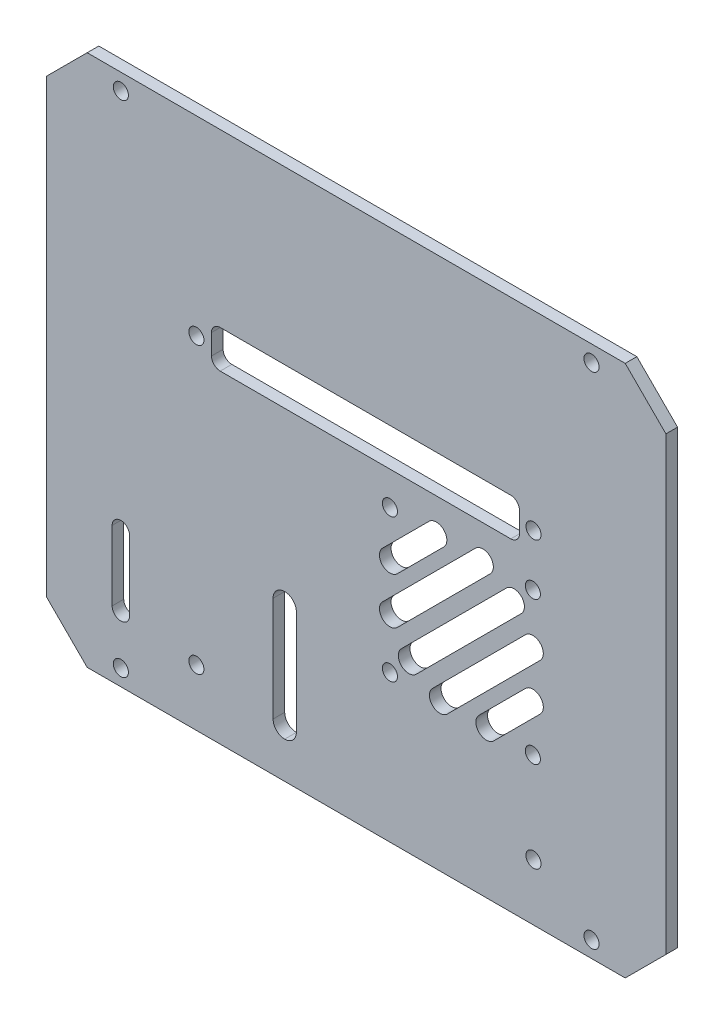
SolidWorks part; units mm, degrees
ref_plane "前视基准面" through (0, 0, 0) normal (0, 0, 1) x (1, 0, 0)
ref_plane "上视基准面" through (0, 0, 0) normal (0, 1, 0) x (1, 0, 0)
ref_plane "右视基准面" through (0, 0, 0) normal (1, 0, 0) x (0, 0, -1)
sketch "草图2" plane through (0, 0, -42.2) normal (0, 0, -1) x (-1, 0, 0)
  line L32 (-57.3467, -34.0538) -> (-50.3426, -41.058)
  line L33 (-50.3426, -41.058) -> (42.2491, -41.058)
  line L34 (42.2491, -41.058) -> (49.2533, -34.0538)
  line L35 (49.2533, -34.0538) -> (49.2533, 43.5378)
  line L36 (49.2533, 43.5378) -> (42.2491, 50.542)
  line L37 (-57.3467, 43.5378) -> (-57.3467, -34.0538)
  line L38 (-50.3426, 50.542) -> (-57.3467, 43.5378)
  line L39 (42.2491, 50.542) -> (-50.3426, 50.542)
  line L40 (-57.3467, -34.0538) -> (-50.3426, -41.058)
  line L41 (-50.3426, -41.058) -> (42.2491, -41.058)
  line L42 (42.2491, -41.058) -> (49.2533, -34.0538)
  line L43 (49.2533, -34.0538) -> (49.2533, 43.5378)
  line L44 (49.2533, 43.5378) -> (42.2491, 50.542)
  line L45 (-57.3467, 43.5378) -> (-57.3467, -34.0538)
  line L46 (-50.3426, 50.542) -> (-57.3467, 43.5378)
  line L47 (42.2491, 50.542) -> (-50.3426, 50.542)
  dimension "D1" = 0.2
extrude "凸台-拉伸1" add sketch "草图2" along normal blind 2
sketch "草图3" plane through (0, 0, -44.2) normal (0, 0, -1) x (-1, 0, 0)
  circle A0 centre (-44.5467, -38.258) radius 1.3
  circle A1 centre (36.4533, -38.258) radius 1.3
  circle A2 centre (-44.5467, 47.742) radius 1.3
  circle A3 centre (36.4533, 47.742) radius 1.3
  dimension "D1" = 2.6
extrude "切除-拉伸1" cut sketch "草图3" against normal through all
sketch "草图4" plane through (0, 0, -44.2) normal (0, 0, -1) x (-1, 0, 0)
  circle A1 centre (23.4533, -31.2932) radius 1.3
  circle A2 centre (23.4533, -31.2932) radius 1.3
  circle A3 centre (-34.5583, -31.2932) radius 1.3
  circle A4 centre (-34.5583, -31.2932) radius 1.3
  circle A5 centre (23.4533, 17.742) radius 1.3
  circle A6 centre (23.4533, 17.742) radius 1.3
  circle A7 centre (-34.5583, 17.742) radius 1.3
  circle A8 centre (-34.5583, 17.742) radius 1.3
  dimension "D1" = 0
  dimension "D2" = 0
  dimension "D3" = 0
  dimension "D4" = 0
extrude "切除-拉伸2" cut sketch "草图4" against normal up to next
sketch "草图5" plane through (0, 0, -44.2) normal (0, 0, -1) x (-1, 0, 0)
  line L0 (-50.4254, -41.258) -> (42.3319, -41.258) construction
  line L1 (-32.1467, 14.542) -> (20.8533, 14.542)
  line L2 (-32.1467, 14.542) -> (-32.1467, 21.042)
  line L3 (-32.1467, 21.042) -> (20.8533, 21.042)
  line L4 (20.8533, 14.542) -> (20.8533, 21.042)
  line L7 (-57.3467, 43.5378) -> (-57.3467, -34.0538) construction
  dimension "D1" = 53
  dimension "D2" = 6.5
  dimension "D3" = 25.2
  dimension "D4" = 55.8
extrude "切除-拉伸3" cut sketch "草图5" against normal up to next
fillet "圆角1" radius 1.5 4 edges at (32.1467, 21.042, -43.2) (32.1467, 14.542, -43.2) (-20.8533, 14.542, -43.2) (-20.8533, 21.042, -43.2)
sketch "草图7" plane through (0, 0, -44.2) normal (0, 0, -1) x (-1, 0, 0)
  line L0 (-59.0467, 44.242) -> (-59.0467, -34.758) construction
  line L1 (42.9533, 52.242) -> (-51.0467, 52.242) construction
  circle A0 centre (-34.4467, 8.842) radius 1.3
  circle A1 centre (-34.4467, -15.758) radius 1.3
  circle A2 centre (-9.8467, 8.842) radius 1.3
  circle A3 centre (-9.8467, -15.758) radius 1.3
  dimension "D1" = 24.6
  dimension "D2" = 24.6
  dimension "D3" = 24.6
  dimension "D4" = 43.4
extrude "切除-拉伸4" cut sketch "草图7" against normal up to next
sketch "草图8" plane through (0, 0, -44.2) normal (0, 0, -1) x (-1, 0, 0)
  line L0 (-34.4467, 8.842) -> (-9.8467, -15.758) construction
  line L1 (-34.4467, 8.842) -> (-9.8467, 8.842) construction
  line L2 (-34.4467, 8.842) -> (-34.4467, -15.758) construction
  line L3 (-34.4467, -15.758) -> (-9.8467, -15.758) construction
  line L4 (-9.8467, 8.842) -> (-9.8467, -15.758) construction
  line L5 (-31.194, 5.5893) -> (-13.0994, -12.5053) construction
  line L6 (-29.9212, 6.8621) -> (-11.8266, -11.2325)
  line L7 (-32.4668, 4.3165) -> (-14.3722, -13.7781)
  line L8 (-34.4467, 0.242) -> (-18.4467, -15.758) construction
  line L9 (-33.1739, 1.5148) -> (-17.1739, -14.4852)
  line L10 (-35.7195, -1.0308) -> (-19.7195, -17.0308)
  line L11 (-25.8467, 8.842) -> (-9.8467, -7.158) construction
  line L12 (-24.5739, 10.1148) -> (-8.5739, -5.8852)
  line L13 (-27.1195, 7.5692) -> (-11.1195, -8.4308)
  line L14 (-17.8467, 8.842) -> (-9.8467, 0.842) construction
  line L15 (-16.5739, 10.1148) -> (-8.5739, 2.1148)
  line L16 (-19.1195, 7.5692) -> (-11.1195, -0.4308)
  line L17 (-34.4467, -7.758) -> (-26.4467, -15.758) construction
  line L18 (-33.1739, -6.4852) -> (-25.1739, -14.4852)
  line L19 (-35.7195, -9.0308) -> (-27.7195, -17.0308)
  line L20 (42.9533, 52.242) -> (-51.0467, 52.242) construction
  line L22 (-59.0467, 44.242) -> (-59.0467, -34.758) construction
  arc A1 (-29.9212, 6.8621) -> (-32.4668, 4.3165) centre (-31.194, 5.5893) ccw
  arc A2 (-14.3722, -13.7781) -> (-11.8266, -11.2325) centre (-13.0994, -12.5053) ccw
  arc A3 (-33.1739, 1.5148) -> (-35.7195, -1.0308) centre (-34.4467, 0.242) ccw
  arc A4 (-19.7195, -17.0308) -> (-17.1739, -14.4852) centre (-18.4467, -15.758) ccw
  arc A5 (-24.5739, 10.1148) -> (-27.1195, 7.5692) centre (-25.8467, 8.842) ccw
  arc A6 (-11.1195, -8.4308) -> (-8.5739, -5.8852) centre (-9.8467, -7.158) ccw
  arc A7 (-16.5739, 10.1148) -> (-19.1195, 7.5692) centre (-17.8467, 8.842) ccw
  arc A8 (-11.1195, -0.4308) -> (-8.5739, 2.1148) centre (-9.8467, 0.842) ccw
  arc A9 (-33.1739, -6.4852) -> (-35.7195, -9.0308) centre (-34.4467, -7.758) ccw
  arc A10 (-27.7195, -17.0308) -> (-25.1739, -14.4852) centre (-26.4467, -15.758) ccw
  point P10 (-22.1467, -3.458)
  point P15 (-26.4467, -7.758)
  point P22 (-17.8467, 0.842)
  point P29 (-13.8467, 4.842)
  point P36 (-30.4467, -11.758)
  dimension "D1" = 1.8
  dimension "D2" = 1.8
  dimension "D3" = 1.8
  dimension "D4" = 1.8
  dimension "D5" = 1.8
  dimension "D6" = 8
  dimension "D7" = 8
  dimension "D8" = 8
  dimension "D9" = 8
  dimension "D10" = 4.6
  dimension "D11" = 4.6
  dimension "D12" = 43.4
  dimension "D13" = 68
  dimension "D14" = 24.6
extrude "切除-拉伸5" cut sketch "草图8" against normal up to next
sketch "草图9" plane through (0, 0, -44.2) normal (0, 0, -1) x (-1, 0, 0)
  line L0 (49.2533, -34.0538) -> (49.2533, 43.5378) construction
  line L1 (6.2533, -12.758) -> (10.2533, -12.758)
  line L2 (6.2533, -12.758) -> (6.2533, -34.758)
  line L3 (6.2533, -34.758) -> (10.2533, -34.758)
  line L4 (10.2533, -12.758) -> (10.2533, -34.758)
  line L6 (-51.0467, -42.758) -> (42.9533, -42.758) construction
  dimension "D1" = 39
  dimension "D2" = 4
  dimension "D3" = 22
  dimension "D4" = 8
extrude "切除-拉伸6" cut sketch "草图9" against normal blind 8
fillet "圆角2" radius 2 4 edges at (-6.2533, -34.758, -43.2) (-10.2533, -34.758, -43.2) (-10.2533, -12.758, -43.2) (-6.2533, -12.758, -43.2)
sketch "草图10" plane through (0, 0, -44.2) normal (0, 0, -1) x (-1, 0, 0)
  line L0 (23.4533, -31.2932) -> (23.4533, -2.7979) construction
  line L1 (36.4533, -38.258) -> (36.4533, -17.4808) construction
  line L2 (36.4533, -17.758) -> (36.4533, -29.758) construction
  line L3 (37.9533, -17.758) -> (37.9533, -29.758)
  line L4 (34.9533, -17.758) -> (34.9533, -29.758)
  line L5 (50.9533, -34.758) -> (50.9533, 44.242) construction
  line L6 (-51.0467, -42.758) -> (42.9533, -42.758) construction
  arc A0 (37.9533, -17.758) -> (34.9533, -17.758) centre (36.4533, -17.758) ccw
  arc A1 (34.9533, -29.758) -> (37.9533, -29.758) centre (36.4533, -29.758) ccw
  point P8 (36.4533, -23.758)
  dimension "D1" = 1.5
  dimension "D2" = 12
  dimension "D3" = 14.5
  dimension "D4" = 13
extrude "切除-拉伸7" cut sketch "草图10" against normal blind 10
